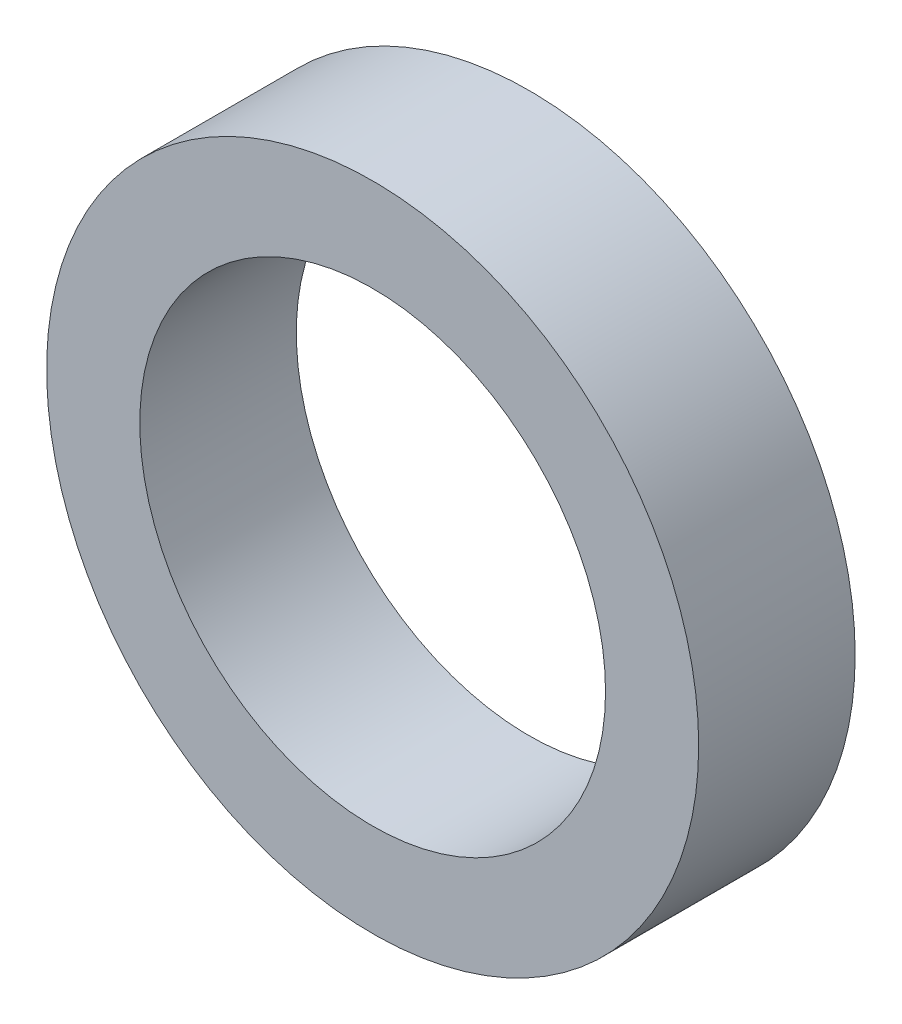
SolidWorks part; units mm, degrees
ref_plane "Front Plane" through (0, 0, 0) normal (1, 0, 0) x (0, 1, 0)
ref_plane "Top Plane" through (0, 0, 0) normal (0, 0, 1) x (0, 1, 0)
ref_plane "Right Plane" through (0, 0, 0) normal (0, 1, 0) x (-1, 0, 0)
sketch "Sketch1" plane through (0, 0, 0) normal (0, 0, 1) x (0, 1, 0)
  circle A0 centre (0, 0) radius 7.9375
  circle A1 centre (0, 0) radius 11.1125
  dimension "D1" = 15.875
  dimension "D2" = 3.175
extrude "Boss-Extrude1" add sketch "Sketch1" along normal blind 5.334
